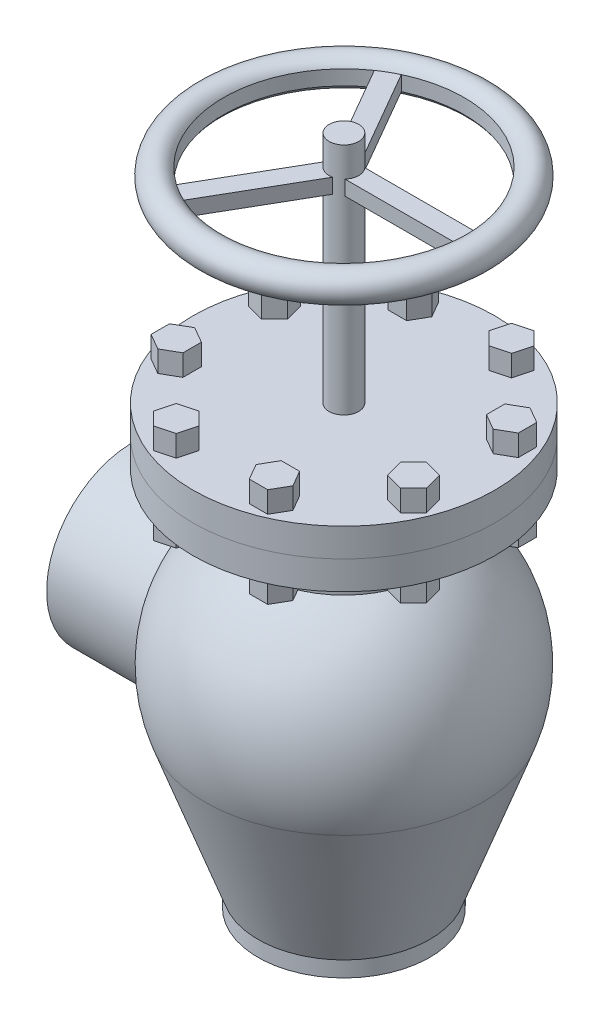
SolidWorks part; units mm, degrees
ref_plane "Front Plane" through (0, 0, 0) normal (0, 0, 1) x (1, 0, 0)
ref_plane "Top Plane" through (0, 0, 0) normal (0, 1, 0) x (1, 0, 0)
ref_plane "Right Plane" through (0, 0, 0) normal (1, 0, 0) x (0, 0, -1)
sketch "Weld End Sketch" plane through (0, 0, 0) normal (1, 0, 0) x (0, 0, -1)
  circle A0 centre (0, 0) radius 72.263
  dimension "A" = 144.526
extrude "Weld End" add sketch "Weld End Sketch" against normal blind 177.8
sketch "Body Sketch" plane through (0, 0, 0) normal (0, 0, 1) x (1, 0, 0)
  line L0 (-72.263, 142.24) -> (-72.263, 101.0546)
  line L1 (0, -199.4458) -> (0, 283.4066) construction
  line L2 (-116.7413, -42.4904) -> (-72.263, -164.6936)
  line L3 (-72.263, -164.6936) -> (-72.263, -177.8)
  line L4 (-72.263, -177.8) -> (0, -177.8)
  line L5 (0, -177.8) -> (0, 142.24)
  line L6 (-72.263, 142.24) -> (0, 142.24)
  line L7 (0, -72.263) -> (0, 72.263) construction
  arc A0 (-72.263, 101.0546) -> (-116.7413, -42.4904) centre (0, 0) ccw
  dimension "D1" = 20
  dimension "E1*.8" = 142.24
  dimension "2*t" = 13.1064
  dimension "A" = 144.526
  dimension "E1" = 177.8
revolve "Body" add sketch "Body Sketch" angle 360 about L1
sketch "Flange Bottom Sketch" plane through (0, 142.24, 0) normal (0, 1, 0) x (-1, 0, 0)
  circle A0 centre (0, 0) radius 127
  dimension "O" = 254
extrude "Flange Bottom" add sketch "Flange Bottom Sketch" along normal blind 23.876
sketch "Flange Top Sketch" plane through (0, 166.116, 0) normal (0, 1, 0) x (-1, 0, 0)
  circle A1 centre (0, 0) radius 127
  circle A2 centre (0, 0) radius 127
  dimension "D1" = 0
extrude "Flange Top" add sketch "Flange Top Sketch" along normal blind 23.876
ref_plane "Driver Plane" through (0, 355.6, 0) normal (0, 1, 0) x (-1, 0, 0)
sketch "Driver Path" plane through (0, 355.6, 0) normal (0, 1, 0) x (-1, 0, 0)
  circle A0 centre (0, 0) radius 124.46
  dimension "D" = 248.92
sketch "Driver Profile" plane through (0, 0, 0) normal (0, 0, 1) x (1, 0, 0)
  line L0 (124.46, 355.6) -> (-124.46, 355.6) construction
  line L1 (-101.2354, 361.823) -> (0, 361.823)
  line L2 (124.46, 355.6) -> (-124.46, 355.6) construction
  line L3 (-101.2354, 349.377) -> (0, 349.377)
  line L4 (0, 361.823) -> (0, 349.377)
  arc A0 (-101.2354, 361.823) -> (-101.2354, 349.377) centre (-112.014, 355.6) ccw
  dimension "D1" = 12.446
  dimension "D/20" = 12.446
sweep "Driver Sweep" add profiles "Driver Profile" path "Driver Path"
sketch "Centre Support Sketch" plane through (0, 361.823, 0) normal (0, 1, 0) x (-1, 0, 0)
  circle A0 centre (0, 0) radius 12.446
  dimension "D/10" = 24.892
extrude "Centre Support" add sketch "Centre Support Sketch" against normal up to surface (171.831 mm away) and the other way blind 24.892 up to face at (0, 189.992, 127)
sketch "Driver Cut Sketch" plane through (0, 361.823, 0) normal (0, 1, 0) x (-1, 0, 0)
  line L0 (0, 0) -> (0, 113.8697) construction
  line L1 (0, 0) -> (-104.7757, 0) construction
  line L2 (43.2617, 91.5262) -> (-2.5474, 12.1825)
  line L3 (-100.8948, -8.2973) -> (-9.2767, -8.2973)
  line L4 (57.6331, 83.2288) -> (11.8241, 3.8852)
  line L5 (-100.8948, 8.2973) -> (-9.2767, 8.2973)
  line L6 (57.6331, -83.2288) -> (11.8241, -3.8852)
  line L7 (43.2617, -91.5262) -> (-2.5474, -12.1825)
  circle A0 centre (0, 0) radius 101.2354 construction
  arc A1 (43.2617, 91.5262) -> (-100.8948, 8.2973) centre (0, 0) ccw
  circle A2 centre (0, 0) radius 12.446 construction
  arc A3 (-9.2767, -8.2973) -> (-2.5474, -12.1825) centre (0, 0) ccw
  arc A4 (-2.5474, 12.1825) -> (-9.2767, 8.2973) centre (0, 0) ccw
  arc A5 (11.8241, -3.8852) -> (11.8241, 3.8852) centre (0, 0) ccw
  arc A6 (57.6331, -83.2288) -> (57.6331, 83.2288) centre (0, 0) ccw
  arc A7 (-100.8948, -8.2973) -> (43.2617, -91.5262) centre (0, 0) ccw
  dimension "D/30" = 8.2973
extrude "Driver Cut" cut sketch "Driver Cut Sketch" against normal up to surface (12.446 mm away) up to face at (0, 349.377, 12.446)
sketch "ID Profile" plane through (-177.8, 0, 0) normal (-1, 0, 0) x (0, 0, 1)
  circle A0 centre (0, 0) radius 65.7098
  circle A1 centre (0, 0) radius 72.263 construction
  dimension "t" = 6.5532
sketch "ID Path" plane through (0, 0, 0) normal (0, 0, 1) x (1, 0, 0)
  line L0 (-177.8, 0) -> (0, 0)
  line L1 (-177.8, 72.263) -> (-177.8, -72.263) construction
  line L2 (0, 0) -> (0, -177.8)
  line L3 (-72.263, -177.8) -> (72.263, -177.8) construction
sweep "ID Cut" cut profiles "ID Profile" path "ID Path"
ref_plane "Bolt Plane" through (0, 207.899, 0) normal (0, 1, 0) x (-1, 0, 0)
sketch "Bolt Sketch" plane through (0, 207.899, 0) normal (0, 1, 0) x (-1, 0, 0)
  line L0 (0, 0) -> (-127.3205, -52.7379) construction
  line L1 (0, 0) -> (-142.2485, 0) construction
  line L2 (-99.7328, -25.8248) -> (-113.144, -33.5677)
  line L3 (-113.144, -33.5677) -> (-113.144, -49.0536)
  line L4 (-113.144, -49.0536) -> (-99.7328, -56.7966)
  line L5 (-99.7328, -56.7966) -> (-86.3216, -49.0536)
  line L6 (-86.3216, -49.0536) -> (-86.3216, -33.5677)
  line L7 (-86.3216, -33.5677) -> (-99.7328, -25.8248)
  circle A0 centre (0, 0) radius 107.95 construction
  circle A2 centre (-99.7328, -41.3107) radius 13.4112 construction
  dimension "BC" = 215.9
  dimension "DH*1.2" = 26.8224
  dimension "Angle" = 22.5
extrude "Bolt" add sketch "Bolt Sketch" against normal blind 83.566
pattern_circular "Bolt Pattern" count 8 every 45 about axis through (0, 166.116, 0) along (0, -1, 0) of "Bolt"
sketch "Sketch1" plane through (0, 0, 0) normal (0, 0, 1) x (1, 0, 0)
  line L0 (127, 166.116) -> (-127, 166.116) construction
  line L1 (127, 166.116) -> (-127, 166.116)
split line "Split Line1"
sketch "CPointSketch" plane through (0, 0, 0) normal (0, 0, 1) x (1, 0, 0)
  line L0 (-177.8, 72.263) -> (-177.8, -72.263) construction
  line L1 (-72.263, -177.8) -> (72.263, -177.8) construction
  point P0 (-177.8, 0)
  point P1 (0, -177.8)
other "CPoint1" parameters "Diameter"=127, "StubLength"=0
ref_axis "Axis1" through (-187.8, 0, 0) along (1, 0, 0)
other "CPoint2" parameters "Diameter"=127, "StubLength"=0
ref_axis "Axis2" through (0, -187.8, 0) along (0, 1, 0)
other "RPoint1"
sketch "Sketch2" plane through (0, 0, 0) normal (0, 1, 0) x (1, 0, 0)
  line L1 (-90.746, -60.5058) -> (90.746, -60.5058)
  line L2 (-90.746, -60.5058) -> (-90.746, 60.5058)
  line L3 (-90.746, 60.5058) -> (90.746, 60.5058)
  line L4 (90.746, -60.5058) -> (90.746, 60.5058)
  line L5 (-90.746, -60.5058) -> (90.746, 60.5058) construction
  line L6 (-90.746, 60.5058) -> (90.746, -60.5058) construction
  point P0 (0, 0)
equation "\"D1@Driver Profile\" = \"D/20@Driver Profile\""
equation "\"D2@Centre Support\" = \"D/10@Centre Support Sketch\""
